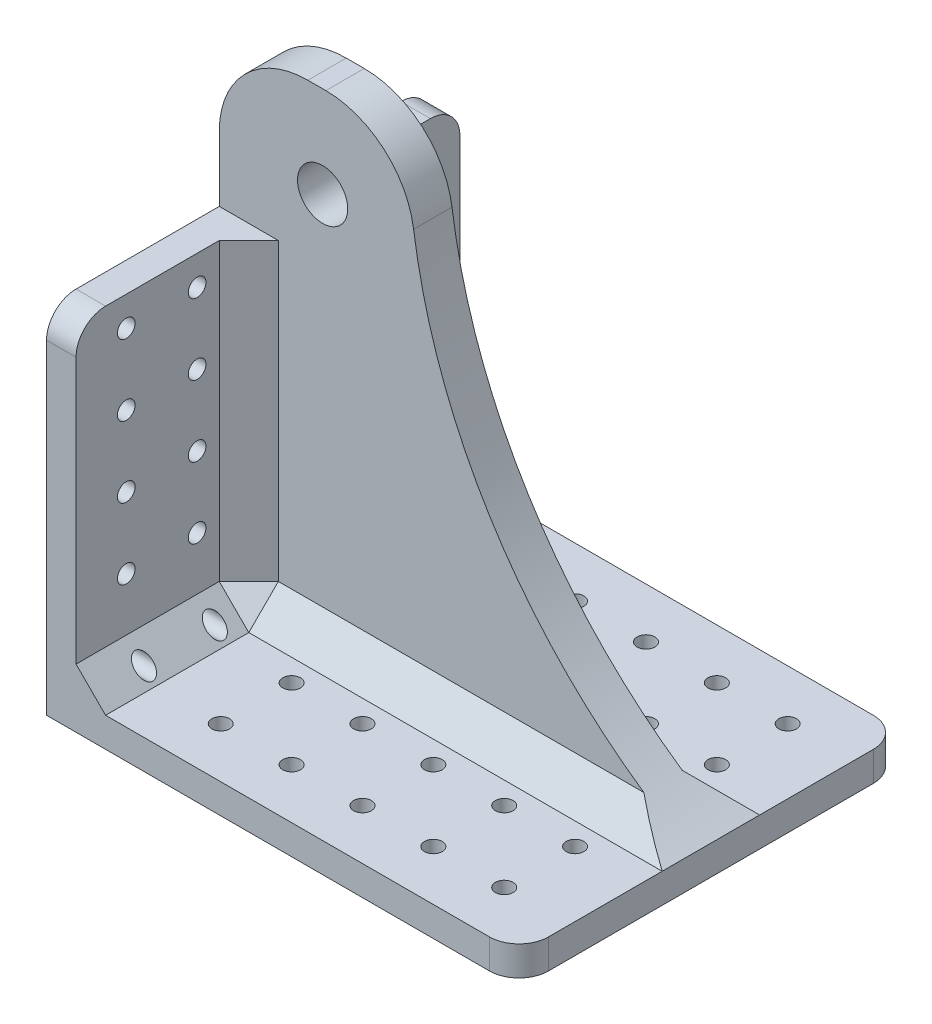
SolidWorks part; units mm, degrees
ref_plane "Front" through (0, 0, 0) normal (0, 0, 1) x (1, 0, 0)
ref_plane "Top" through (0, 0, 0) normal (0, 1, 0) x (1, 0, 0)
ref_plane "Right" through (0, 0, 0) normal (1, 0, 0) x (0, 0, -1)
sketch "Esquisse1" plane through (0, 0, 0) normal (0, 0, 1) x (1, 0, 0)
  line L0 (0, 0) -> (80, 0)
  line L1 (80, 0) -> (80, 5)
  line L2 (80, 5) -> (5, 5)
  line L3 (5, 5) -> (5, 60)
  line L4 (5, 60) -> (0, 60)
  line L5 (0, 60) -> (0, 0)
  dimension "D1" = 60
  dimension "D2" = 80
  dimension "D3" = 5
  dimension "D4" = 5
extrude "Boss.-Extru.1" add sketch "Esquisse1" along normal blind 65
sketch "Esquisse2" plane through (0, 5, 0) normal (0, 1, 0) x (1, 0, 0)
  line L0 (80, -32.5) -> (0, -32.5) construction
  line L1 (80, -65) -> (80, 0) construction
  line L3 (0, -35.75) -> (0, -29.25)
  line L5 (0, -29.25) -> (80, -29.25)
  line L6 (80, -29.25) -> (80, -35.75)
  line L7 (0, -35.75) -> (80, -35.75)
  line L8 (0, -65) -> (0, 0) construction
  point P5 (0, -32.5)
  point P9 (0, -29.25)
  point P12 (0, 0)
  point P13 (0, 0)
  point P15 (0, 0)
  dimension "D1" = 6.5
extrude "Boss.-Extru.2" add sketch "Esquisse2" along normal blind 81
sketch "Esquisse3" plane through (0, 0, 35.75) normal (0, 0, 1) x (1, 0, 0)
  line L0 (80, 86) -> (80, 5) construction
  line L1 (32, 86) -> (32, 107.0984) construction
  line L2 (0, 86) -> (80, 86) construction
  line L3 (32, 86) -> (80, 86)
  line L4 (80, 86) -> (80, 5)
  line L5 (0, 86) -> (0, 60) construction
  arc A0 (80, 5) -> (32, 86) centre (124.3437, 86) cw
  dimension "D1" = 32
extrude "Enlèv. mat.-Extru.1" cut sketch "Esquisse3" against normal through all both and the other way through all
fillet "Congé1" radius 15 2 edges at (0, 86, 32.5) (32, 86, 32.5)
sketch "Esquisse4" plane through (0, 0, 35.75) normal (0, 0, 1) x (1, 0, 0)
  line L0 (0, 60) -> (0, 0) construction
  line L1 (5, 60) -> (0, 60) construction
  circle A0 centre (17.5, 70.5) radius 4.25
  dimension "D2" = 10.5
  dimension "D3" = 8.5
  dimension "D1" = 17.5
extrude "Enlèv. mat.-Extru.2" cut sketch "Esquisse4" against normal through all both and the other way through all
chamfer "Chanfrein1" distance 5 angle 45 6 edges at (5, 5, 14.625) (42.5, 5, 29.25) (5, 32.5, 29.25) (5, 32.5, 35.75) (42.5, 5, 35.75) (5, 5, 50.375)
sketch "Esquisse5" plane through (0, 0, 0) normal (-1, 0, 0) x (0, 0, 1)
  line L0 (32.5, 0) -> (32.5, 62) construction
  line L1 (65, 0) -> (0, 0) construction
  line L3 (32.5, 31) -> (0, 31) construction
  line L5 (14.5, 31) -> (14.5, 55.0962) construction
  line L6 (8.5, 55) -> (8.5, 43) construction
  line L7 (8.5, 43) -> (8.5, 31) construction
  line L8 (20.5, 43) -> (20.5, 31) construction
  line L9 (20.5, 55) -> (20.5, 43) construction
  line L10 (20.5, 7) -> (20.5, 19) construction
  line L11 (8.5, 7) -> (8.5, 19) construction
  line L12 (56.5, 7) -> (56.5, 19) construction
  line L13 (44.5, 7) -> (44.5, 19) construction
  line L14 (44.5, 55) -> (44.5, 43) construction
  line L15 (44.5, 43) -> (44.5, 31) construction
  line L16 (56.5, 43) -> (56.5, 31) construction
  line L17 (56.5, 55) -> (56.5, 43) construction
  line L18 (50.5, 31) -> (50.5, 55.0962) construction
  line L19 (65, 60) -> (35.75, 60) construction
  circle A0 centre (8.5, 55) radius 1.5
  circle A1 centre (8.5, 43) radius 1.5
  circle A2 centre (8.5, 31) radius 1.5
  circle A3 centre (20.5, 31) radius 1.5
  circle A4 centre (20.5, 43) radius 1.5
  circle A5 centre (20.5, 55) radius 1.5
  circle A6 centre (20.5, 7) radius 1.5
  circle A7 centre (20.5, 19) radius 1.5
  circle A8 centre (8.5, 19) radius 1.5
  circle A9 centre (8.5, 7) radius 1.5
  circle A10 centre (56.5, 7) radius 1.5
  circle A11 centre (56.5, 19) radius 1.5
  circle A12 centre (44.5, 19) radius 1.5
  circle A13 centre (44.5, 7) radius 1.5
  circle A14 centre (44.5, 55) radius 1.5
  circle A15 centre (44.5, 43) radius 1.5
  circle A16 centre (44.5, 31) radius 1.5
  circle A17 centre (56.5, 31) radius 1.5
  circle A18 centre (56.5, 43) radius 1.5
  circle A19 centre (56.5, 55) radius 1.5
  point P5 (32.5, 60)
  point P6 (0, 0)
  point P9 (32.5, 62.7074)
  point P54 (0, 0)
  point P55 (32.5, 60)
  point P56 (0, 0)
  point P57 (0, 0)
  dimension "D1" = 3
  dimension "D2" = 12
  dimension "D4" = 24
  dimension "D5" = 12
  dimension "D3" = 18
  dimension "D6" = 2
extrude "Enlèv. mat.-Extru.3" cut sketch "Esquisse5" against normal through all both and the other way through all
fillet "Congé2" radius 5 4 edges at (80, 2.5, 0) (80, 2.5, 65) (2.5, 60, 0) (2.5, 60, 65)
sketch "Esquisse6" plane through (0, 0, 0) normal (0, -1, 0) x (1, 0, 0)
  line L0 (0, 32.5) -> (90, 32.5) construction
  line L1 (0, 65) -> (0, 0) construction
  line L2 (45, 32.5) -> (45, 56.5) construction
  line L3 (45, 56.5) -> (57, 56.5) construction
  line L4 (57, 56.5) -> (57, 61.2046) construction
  line L5 (33, 56.5) -> (33, 61.2046) construction
  line L6 (45, 44.5) -> (60.4343, 44.5) construction
  line L7 (45, 50.5) -> (49.2932, 50.5) construction
  line L8 (45, 44.5) -> (57, 44.5) construction
  line L9 (45, 20.5) -> (57, 20.5) construction
  line L10 (45, 14.5) -> (49.2932, 14.5) construction
  line L11 (45, 20.5) -> (60.4343, 20.5) construction
  line L12 (45, 8.5) -> (57, 8.5) construction
  circle A0 centre (45, 56.5) radius 1.5
  circle A1 centre (57, 56.5) radius 1.5
  circle A2 centre (69, 56.5) radius 1.5
  circle A3 centre (21, 56.5) radius 1.5
  circle A4 centre (33, 56.5) radius 1.5
  circle A5 centre (33, 44.5) radius 1.5
  circle A6 centre (21, 44.5) radius 1.5
  circle A7 centre (69, 44.5) radius 1.5
  circle A8 centre (57, 44.5) radius 1.5
  circle A9 centre (45, 44.5) radius 1.5
  circle A10 centre (45, 20.5) radius 1.5
  circle A11 centre (57, 20.5) radius 1.5
  circle A12 centre (69, 20.5) radius 1.5
  circle A13 centre (21, 20.5) radius 1.5
  circle A14 centre (33, 20.5) radius 1.5
  circle A15 centre (33, 8.5) radius 1.5
  circle A16 centre (21, 8.5) radius 1.5
  circle A17 centre (69, 8.5) radius 1.5
  circle A18 centre (57, 8.5) radius 1.5
  circle A19 centre (45, 8.5) radius 1.5
  point P32 (52, 56.5)
  dimension "D1" = 3
  dimension "D2" = 12
  dimension "D4" = 12
  dimension "D5" = 90
extrude "Enlèv. mat.-Extru.4" cut sketch "Esquisse6" against normal through all both and the other way through all
